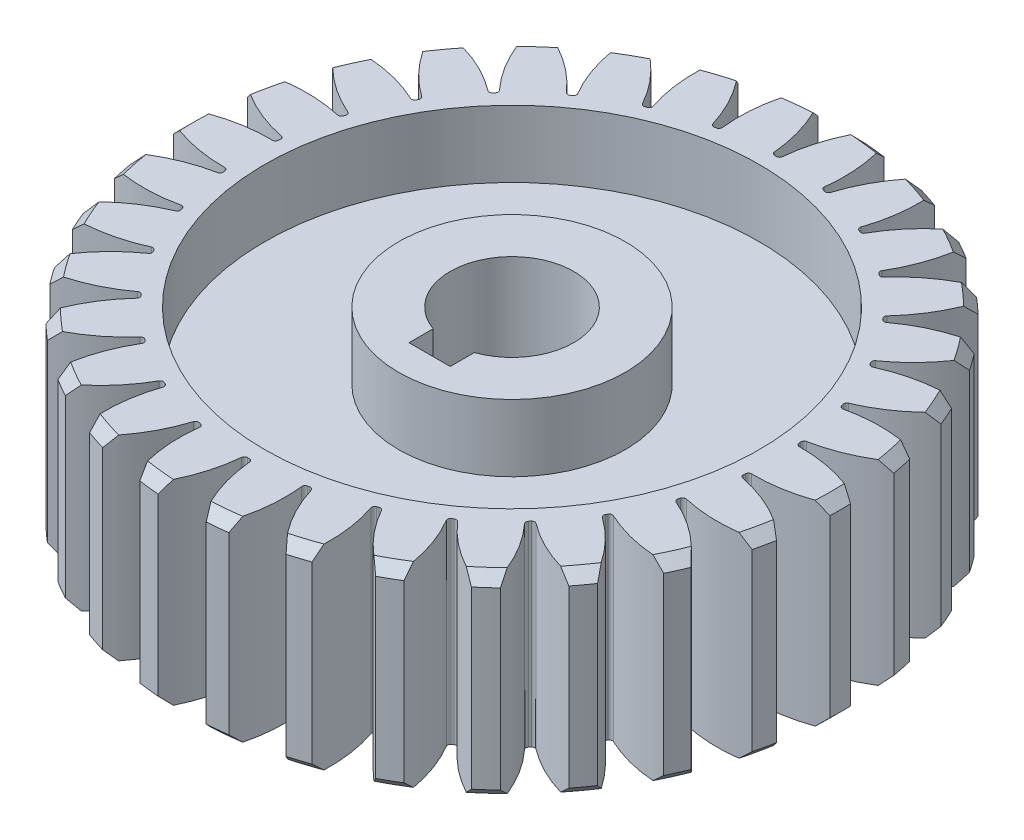
SolidWorks part; units mm, degrees
ref_plane "Front Plane" through (0, 0, 0) normal (1, 0, 0) x (0, 1, 0)
ref_plane "Top Plane" through (0, 0, 0) normal (0, 0, 1) x (0, 1, 0)
ref_plane "Right Plane" through (0, 0, 0) normal (0, 1, 0) x (-1, 0, 0)
sketch "Sketch2" plane through (0, 0, 0) normal (0, 1, 0) x (-1, 0, 0)
  line L0 (0, 0) -> (50000, 0) construction
  line L1 (0, 0) -> (0, 50000) construction
  line L4 (-2, 5.6569) -> (-2, 8)
  line L5 (-2, 8) -> (2, 8)
  line L6 (2, 5.6569) -> (2, 8)
  arc A0 (-2, 5.6569) -> (2, 5.6569) centre (0, 0) ccw
  circle A1 centre (0, 0) radius 11
  point P3 (0, 6)
  dimension "D1" = 12
  dimension "D4" = 22
  dimension "D2" = 4
  dimension "D3" = 8
extrude "Boss-Extrude1" add sketch "Sketch2" along normal mid plane 19
sketch "Sketch3" plane through (0, 0, 0) normal (1, 0, 0) x (0, 1, 0)
  line L0 (0, 0) -> (-50000, 0) construction
  line L1 (0, 0) -> (0, 50000) construction
sketch "Sketch4" plane through (0, 0, 0) normal (0, 1, 0) x (-1, 0, 0)
  circle A0 centre (0, 0) radius 24
  circle A1 centre (0, 0) radius 25.5
  dimension "D1" = 48
  dimension "D2" = 51
extrude "Boss-Extrude2" add sketch "Sketch4" along normal mid plane 6 contours A0 region at (0, 0, 0)
extrude "Boss-Extrude3" add sketch "Sketch4<3>" along normal mid plane 19
sketch "Sketch4<3>" plane through (0, 0, 0) normal (0, 1, 0) x (-1, 0, 0) same geometry as "Sketch4"
extrude "Cut-Extrude2" cut sketch "Sketch2<4>" against normal through all both and the other way through all contours A0 L6 L5 L4
sketch "Sketch2<4>" plane through (0, 0, 0) normal (0, 1, 0) x (-1, 0, 0) same geometry as "Sketch2"
sketch "Sketch6" plane through (0, 0, 0) normal (0, 1, 0) x (-1, 0, 0)
  line L0 (0, 25.8) -> (0.6394, 25.8) construction
  line L1 (-2.2322, 31.922) -> (0, 0) construction
  line L2 (0, -200000) -> (0, 250000) construction
  line L3 (0, 0) -> (0, 46.9929) construction
  line L4 (-3.2287, 31.8367) -> (0, 0) construction
  arc A0 (-4.222, 31.7203) -> (-2.2322, 31.922) centre (0, 0) cw
  arc A1 (-0.2988, 25.7736) -> (0, 25.5) centre (0, 25.8) ccw
  circle A2 centre (0, 0) radius 25.5 construction
  arc A3 (-2.2322, 31.922) -> (-0.2988, 25.7736) centre (-15.2406, 24.4534) cw
  arc A4 (-4.8816, 25.3088) -> (-5.1195, 24.9808) centre (-5.1797, 25.2747) cw
  arc A5 (-4.222, 31.7203) -> (-4.8816, 25.3088) centre (10.021, 27.0153) ccw
  arc A6 (-5.1195, 24.9808) -> (0, 25.5) centre (0, 0) cw
  dimension "D1" = 32
  dimension "D4" = 0.6
  dimension "D5" = 15
  dimension "D2" = 2
  dimension "D3" = 4
extrude "Boss-Extrude5" add sketch "Sketch6" along normal mid plane 19
chamfer "Chamfer1" distance 1 angle 45 2 edges at (3.2287, -9.5, 31.8367) (3.2287, 9.5, 31.8367) tangent propagation no
pattern_circular "CirPattern2" count 30 over 360 about axis through (0, 9.5, 0) along (0, 1, 0) of "Boss-Extrude5", "Chamfer1"
